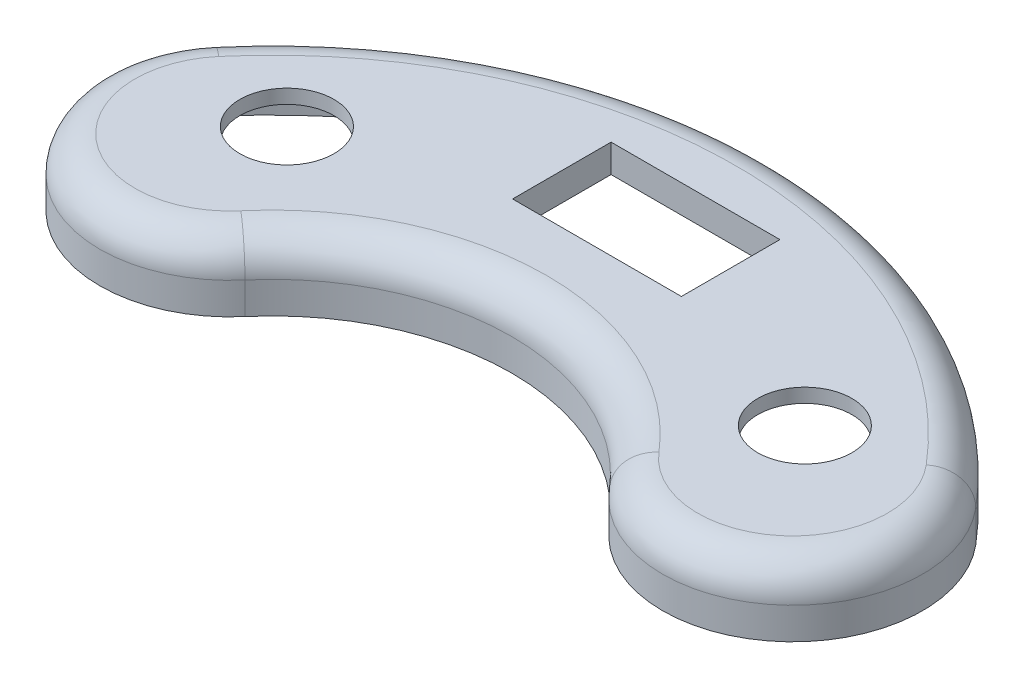
SolidWorks part; units mm, degrees
ref_plane "Front Plane" through (0, 0, 0) normal (0, 0, 1) x (1, 0, 0)
ref_plane "Top Plane" through (0, 0, 0) normal (0, 1, 0) x (1, 0, 0)
ref_plane "Right Plane" through (0, 0, 0) normal (1, 0, 0) x (0, 0, -1)
sketch "Sketch2" plane through (0, 0, 0) normal (0, 1, 0) x (1, 0, 0)
  arc A0 (-43.6936, 0) -> (57.9064, 0) centre (7.1064, -43.0279) cw construction
  arc A1 (73.8768, 13.527) -> (-59.6641, 13.527) centre (7.1064, -43.0279) ccw
  arc A2 (41.9359, -13.527) -> (-27.7232, -13.527) centre (7.1064, -43.0279) ccw
  arc A3 (41.9359, -13.527) -> (73.8768, 13.527) centre (57.9064, 0) ccw
  arc A4 (-59.6641, 13.527) -> (-27.7232, -13.527) centre (-43.6936, 0) ccw
  point P3 (7.1064, 23.5457)
  point P8 (7.1064, 2.6164)
  dimension "D1" = 50.8
  dimension "D2" = 50.8
extrude "Boss-Extrude1" add sketch "Sketch2" along normal blind 19.05
fillet "Fillet1" radius 3.81 4 edges at (7.1064, 19.05, -2.6164) (-57.2207, 19.05, 15.9704) (7.1064, 19.05, -44.475) (71.4334, 19.05, 15.9704)
fillet "Fillet2" radius 3.81 4 edges at (7.1064, 0, -44.475) (-57.2207, 0, 15.9704) (7.1064, 0, -2.6164) (71.4334, 0, 15.9704)
sketch "Sketch3" plane through (0, 19.05, 0) normal (0, 1, 0) x (1, 0, 0)
  line L1 (-56.7568, 11.0646) -> (70.9695, 11.0646) construction
  line L2 (-10.4904, 35.6265) -> (-10.4904, 12.7665)
  line L3 (-10.4904, 35.6265) -> (25.0696, 35.6265)
  line L4 (-10.4904, 12.7665) -> (25.0696, 12.7665)
  line L5 (25.0696, 35.6265) -> (25.0696, 12.7665)
  line L6 (-10.4904, 35.6265) -> (25.0696, 35.6265) construction
  point P16 (7.2896, 35.6265)
  dimension "D1" = 22.86
  dimension "D2" = 35.56
extrude "Cut-Extrude1" cut sketch "Sketch3" against normal blind 2.54 contours L2 L4 L5 L3
shell "Shell7" thickness 2.54 removed face at (7.2896, 16.51, -24.1965) outward yes
sketch "Sketch6" plane through (0, 21.59, 0) normal (0, 1, 0) x (1, 0, 0)
  line L0 (53.8552, 6.2606) -> (80.5252, 6.2606) construction
  line L1 (-39.6425, 6.2606) -> (-66.3125, 6.2606) construction
  circle A0 centre (-39.6425, 6.2606) radius 8.5
  arc A1 (-61.6022, 15.1687) -> (-25.785, -15.1687) centre (-43.6936, 0) ccw construction
  circle A2 centre (53.8552, 6.2606) radius 8.5
  arc A3 (39.9978, -15.1687) -> (75.815, 15.1687) centre (57.9064, 0) ccw construction
  dimension "D1" = 26.67
  dimension "D2" = 26.67
extrude "Cut-Extrude2" cut sketch "Sketch6" against normal blind 2.54
ref_plane "Plane1" through (0, 9.525, 0) normal (0, 1, 0) x (1, 0, 0)
other "SurfaceCut1"
